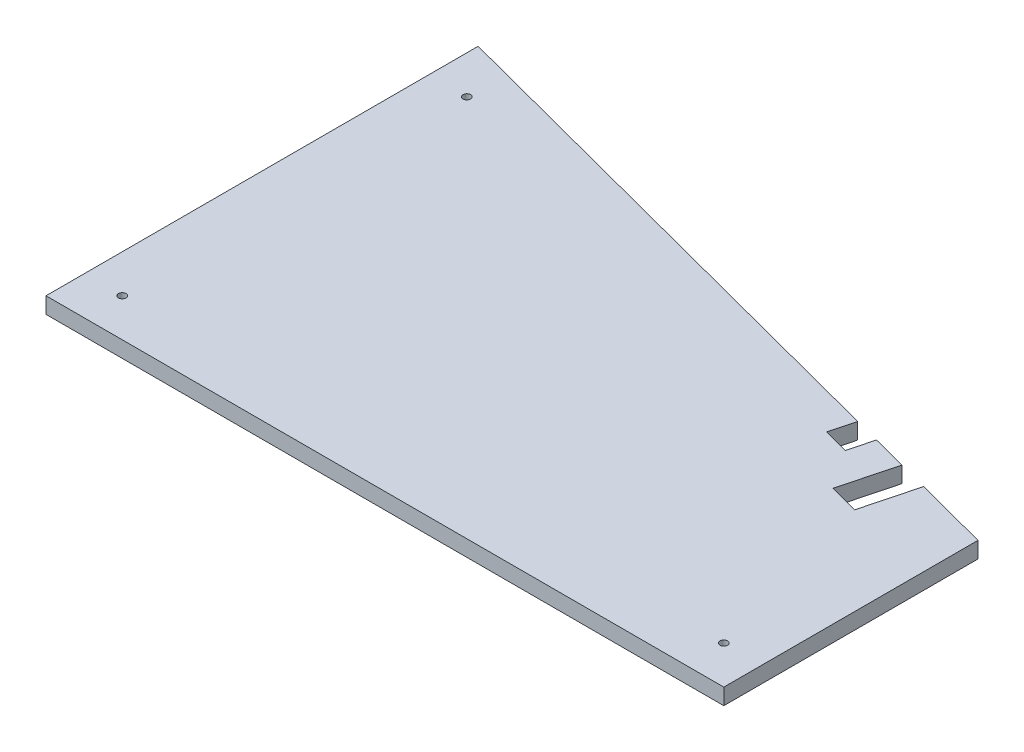
SolidWorks part; units mm, degrees
material "Balsa"
ref_plane "Front Plane" through (0, 0, 0) normal (0, 0, 1) x (1, 0, 0)
ref_plane "Top Plane" through (0, 0, 0) normal (0, 1, 0) x (1, 0, 0)
ref_plane "Right Plane" through (0, 0, 0) normal (1, 0, 0) x (0, 0, -1)
sketch "Sketch2" plane through (0, 0, 0) normal (0, 1, 0) x (1, 0, 0)
  line L0 (0, 0) -> (266.65, 0)
  line L1 (266.65, 0) -> (266.65, 100)
  line L2 (266.65, 100) -> (237.6332, 107.6174)
  line L4 (226.0265, 110.6643) -> (220.3896, 89.1919)
  line L5 (220.3896, 89.1919) -> (231.9963, 86.1449)
  line L6 (231.9963, 86.1449) -> (237.6332, 107.6174)
  line L7 (226.0265, 110.6643) -> (212.4853, 114.2191)
  line L8 (209.9462, 104.5469) -> (199.9462, 107.172)
  line L9 (199.9462, 107.172) -> (202.4853, 116.8443)
  line L10 (209.9462, 104.5469) -> (212.4853, 114.2191)
  line L11 (202.4853, 116.8443) -> (0, 170)
  line L16 (0, 170) -> (0, 0)
  point P10 (214.9954, 103.1502)
  point P12 (0, 0)
  point P14 (0, 0)
  point P15 (0, 0)
  point P16 (225.5772, 100)
  point P17 (239.539, 89.4928)
  point P18 (251.1561, 86.2955)
  dimension "D1" = 170
  dimension "D2" = 100
  dimension "D3" = 266.65
  dimension "D4" = 30
  dimension "D5" = 12
  dimension "D6" = 14
  dimension "D7" = 10
  dimension "D8" = 10
  dimension "D9" = 22.2
extrude "Boss-Extrude1" add sketch "Sketch2" along normal blind 6.35
sketch "Sketch3" plane through (0, 6.35, 0) normal (0, 1, 0) x (1, 0, 0)
  line L0 (0, 0) -> (266.65, 0) construction
  line L1 (0, 170) -> (0, 0) construction
  line L3 (202.4853, 116.8443) -> (0, 170) construction
  line L4 (266.65, 0) -> (266.65, 100) construction
  circle A0 centre (15, 150.554) radius 1.5
  circle A1 centre (15, 15) radius 1.5
  circle A2 centre (251.65, 15) radius 1.5
  dimension "D1" = 3
  dimension "D2" = 3
  dimension "D3" = 3
  dimension "D4" = 15
  dimension "D5" = 15
  dimension "D6" = 15
  dimension "D7" = 15
  dimension "D8" = 15
  dimension "D9" = 15
extrude "Cut-Extrude1" cut sketch "Sketch3" against normal through all
